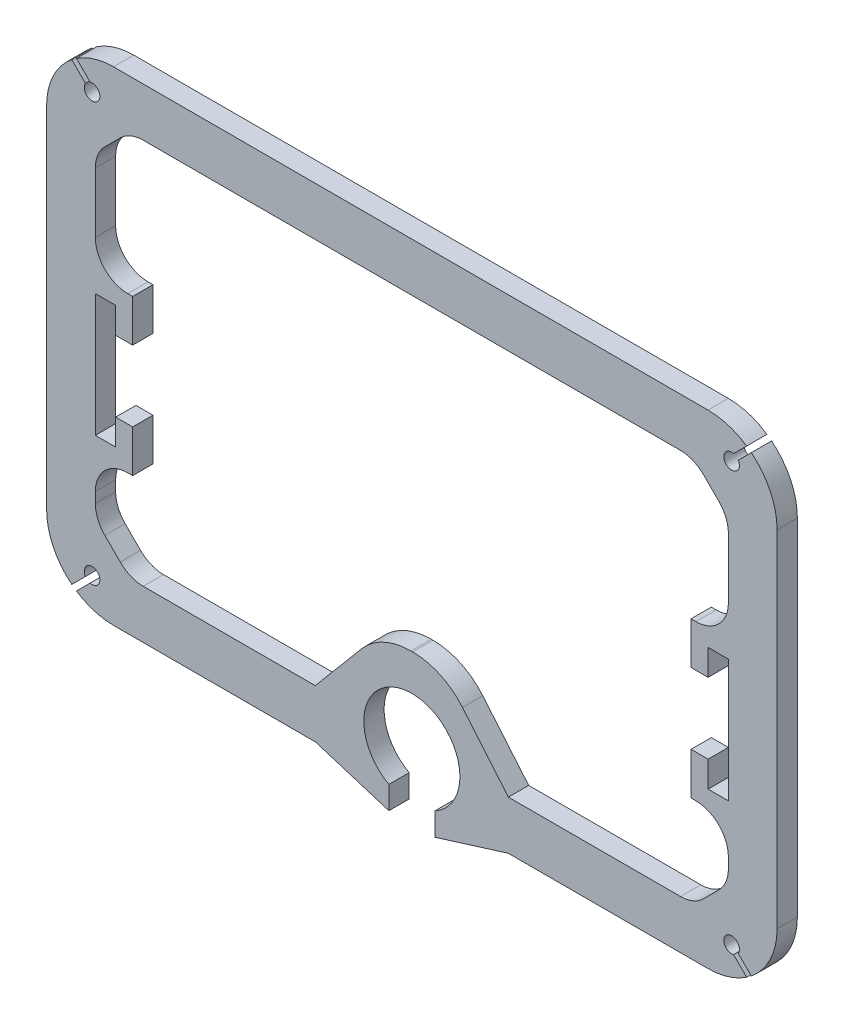
SolidWorks part; units mm, degrees
material "Delrin 2700 NC010, Low Viscosity Acetal Copolymer (SS)"
ref_plane "Front Plane" through (0, 0, 0) normal (0, 0, 1) x (1, 0, 0)
ref_plane "Top Plane" through (0, 0, 0) normal (0, 1, 0) x (1, 0, 0)
ref_plane "Right Plane" through (0, 0, 0) normal (1, 0, 0) x (0, 0, -1)
sketch "Sketch1" plane through (0, 0, 0) normal (0, 0, 1) x (1, 0, 0)
  line L0 (-23.3423, -18.923) -> (-7.5425, -18.923)
  line L1 (-24.765, 13.6903) -> (-24.765, -13.6903)
  line L2 (-23.3423, -15.113) -> (-7.5521, -15.113)
  line L3 (7.5521, -15.113) -> (23.1704, -15.113)
  line L4 (24.765, 13.5184) -> (24.765, -13.5184)
  line L5 (-1000, 0) -> (49000, 0) construction
  line L6 (-1.7968, -18.923) -> (-1.7968, -20.7107)
  line L7 (7.5425, -18.923) -> (23.1704, -18.923)
  line L8 (23.1704, 15.113) -> (-23.3423, 15.113)
  line L9 (-7.5521, -15.113) -> (-3.9596, -10.8316)
  line L10 (-28.575, 13.6903) -> (-28.575, -13.6903)
  line L11 (7.5521, -15.113) -> (3.9596, -10.8316)
  line L12 (-0.0681, -9.017) -> (0.0681, -9.017)
  line L13 (28.575, 13.5184) -> (28.575, -13.5184)
  line L14 (23.1704, 18.923) -> (-23.3423, 18.923)
  line L15 (1.7968, -18.923) -> (1.7968, -20.7107)
  line L16 (-7.5425, -18.923) -> (-1.7968, -20.7107)
  line L17 (7.5425, -18.923) -> (1.7968, -20.7107)
  line L18 (0, 12.5532) -> (0, -24.2768) construction
  line L19 (1.7968, -18.923) -> (23.1704, -18.923) construction
  line L20 (-23.3423, -18.923) -> (-1.7968, -18.923) construction
  line L21 (-24.765, 5.0849) -> (0, 5.0849) construction
  line L22 (0, 5.0849) -> (24.765, 5.0849) construction
  arc A0 (1.7968, -18.923) -> (-1.7968, -18.923) centre (0, -15.621) ccw
  arc A1 (-23.3423, -15.113) -> (-24.765, -13.6903) centre (-23.3423, -13.6903) cw
  arc A2 (-0.0681, -9.017) -> (-3.9596, -10.8316) centre (-0.0681, -14.097) ccw
  arc A3 (24.765, -13.5184) -> (23.1704, -15.113) centre (23.1704, -13.5184) cw
  arc A4 (23.1704, 15.113) -> (24.765, 13.5184) centre (23.1704, 13.5184) cw
  arc A5 (-23.3423, -18.923) -> (-28.575, -13.6903) centre (-23.3423, -13.6903) cw
  arc A6 (28.575, -13.5184) -> (23.1704, -18.923) centre (23.1704, -13.5184) cw
  arc A7 (23.1704, 18.923) -> (28.575, 13.5184) centre (23.1704, 13.5184) cw
  arc A8 (-23.3423, 18.923) -> (-28.575, 13.6903) centre (-23.3423, 13.6903) ccw
  circle A9 centre (-25.019, 16.383) radius 0.6096
  circle A10 centre (25.019, 16.383) radius 0.6096
  arc A11 (-23.3423, 15.113) -> (-24.765, 13.6903) centre (-23.3423, 13.6903) ccw
  arc A12 (0.0681, -9.017) -> (3.9596, -10.8316) centre (0.0681, -14.097) cw
  circle A13 centre (25.019, -16.383) radius 0.6096
  circle A14 centre (-25.019, -16.383) radius 0.6096
  circle A15 centre (0, -15.621) radius 5.3975 construction
  arc A18 (7.5521, -15.113) -> (-7.5521, -15.113) centre (0, -15.621) ccw construction
  point P0 (0, 0)
  dimension "D4" = 3.302
  dimension "D6" = 37.846
  dimension "D7" = 3.556
  dimension "D8" = 3.81
  dimension "D9" = 6.604
  dimension "D5" = 1.2192
  dimension "D2" = 49.53
  dimension "D3" = 7.5184
  dimension "D10" = 5.08
  dimension "D11" = 5.08
  dimension "D14" = 10.795
  dimension "D12" = 2.54
extrude "Boss-Extrude1" add sketch "Sketch1" along normal blind 1.5875
sketch "Sketch2" plane through (-24.765, 0, 0) normal (1, 0, 0) x (0, 0, -1)
  line L0 (0, 2.8448) -> (-1.5875, 2.8448)
  line L1 (0, -6.7596) -> (-1.5875, -6.7596) construction
  line L2 (-1.5875, -15.113) -> (0, -15.113)
  line L3 (-1.5875, -15.113) -> (0, -15.113) construction
  line L4 (0, -13.6903) -> (0, 13.6903)
  line L5 (0, 13.6903) -> (-1.5875, 13.6903)
  line L6 (-1.5875, 13.6903) -> (-1.5875, -13.6903)
  line L7 (0, 13.6903) -> (-1.5875, 13.6903)
  line L8 (0, -13.6903) -> (0, 4.1148)
  line L9 (-1.5875, -15.113) -> (-1.5875, -8.0296)
  line L10 (-1.5875, 4.1148) -> (-1.5875, -13.6903)
  line L11 (-1.5875, -13.6903) -> (0, -13.6903)
  line L12 (0, -15.113) -> (0, -8.0296)
  line L13 (0, 4.1148) -> (-1.5875, 4.1148)
  line L14 (-1.5875, 2.8448) -> (-1.5875, -6.6447)
  line L15 (-1.5875, 4.1148) -> (-1.5875, 2.8448)
  line L16 (0, 2.8448) -> (0, 4.1148)
  line L17 (0, -7.9147) -> (0, 1.4693)
  line L18 (-1.5875, -7.9147) -> (-1.5875, -6.6447)
  line L19 (0, -6.7596) -> (-1.5875, -6.7596)
  line L21 (0, -8.0296) -> (-1.5875, -8.0296)
  line L22 (0, -8.0296) -> (0, -13.6903)
  line L23 (-1.5875, -8.0296) -> (-1.5875, -13.6903)
  line L24 (47.9467, 2.8448) -> (1.4151, 2.8448) construction
  line L28 (-1.5875, -13.6903) -> (0, -13.6903)
  line L29 (47.5608, -9.6909) -> (1.4354, -6.848) construction
  line M5 (0, -13.6903) -> (0, 13.6903)
  line M7 (-1.5875, 13.6903) -> (-1.5875, -13.6903)
  dimension "D1" = 0
  dimension "D2" = 1.27
  dimension "D4" = 1.27
extrude "Boss-Extrude2" add sketch "Sketch2" along normal blind 2.921 contours L13 L10 L0 M5 | L19 L17 L8 L0 L10 M7 | L21 L8 L19 L18 M5 M7 region at (-24.765, -1.9574, 0.7937) region at (-24.765, 3.4798, 0.7937) region at (-24.765, -7.3946, 0.7937)
extrude "Cut-Extrude1" cut sketch "Sketch2<3>" along normal blind 1.5875 contours L19 L17 L0 M5 M7 region at (-24.765, -1.9574, 0.7937)
sketch "Sketch2<3>" plane through (-24.765, 0, 0) normal (1, 0, 0) x (0, 0, -1) same geometry as "Sketch2"
sketch "Sketch3" plane through (-23.1775, 0, 0) normal (-1, 0, 0) x (0, 0, 1)
  line L0 (0, 2.8448) -> (1.5875, 2.8448) construction
  line L1 (0, -6.7596) -> (1.5875, -6.7596) construction
  line L2 (0, 2.8448) -> (1.5875, 2.8448)
  line L3 (0, -6.7596) -> (1.5875, -6.7596)
  line L4 (0, 0.8128) -> (1.5875, 0.8128)
  line L5 (0, -4.7276) -> (1.5875, -4.7276)
  line L6 (1.5875, 0.8128) -> (1.5875, -4.7276)
  line L7 (0, -4.7276) -> (0, 0.8128)
  line M2 (1.5875, -6.7596) -> (1.5875, 2.8448)
  line M4 (0, 2.8448) -> (0, -6.7596)
  dimension "D1" = 2.032
  dimension "D2" = 2.032
extrude "Cut-Extrude2" cut sketch "Sketch3" against normal up to surface (1.3335 mm away) contours L5 L4 M4 M2 region at (-23.1775, -1.9574, 0.7937) up to face at (-21.844, -1.9574, 0.7937)
mirror "Mirror1" about plane through (0, 0, 0) normal (1, 0, 0) of "Cut-Extrude2", "Boss-Extrude2", "Cut-Extrude1"
fillet "Fillet5" radius 2.54 4 edges at (24.765, 4.1148, 0.7937) (24.765, -8.0296, 0.7937) (-24.765, -8.0296, 0.7937) (-24.765, 4.1148, 0.7937)
sketch "Sketch4" plane through (0, 0, 1.5875) normal (0, 0, 1) x (1, 0, 0)
  line L0 (-26.2434, 18.0452) -> (-25.1714, 16.9732)
  line L1 (-26.6067, 17.7799) -> (-25.5348, 16.708)
  line L2 (23.1704, 18.923) -> (-23.3423, 18.923) construction
  circle A0 centre (-25.019, 16.383) radius 0.6096 construction
  arc A1 (-23.3423, 18.923) -> (-28.575, 13.6903) centre (-23.3423, 13.6903) ccw construction
  arc A2 (-26.2434, 18.0452) -> (-26.6067, 17.7799) centre (-23.3423, 13.6903) ccw
  arc A3 (-25.1714, 16.9732) -> (-25.5348, 16.708) centre (-25.019, 16.383) ccw
  dimension "SnapInSlot" = 0.4445
  dimension "D2" = 45
extrude "Slot for installing carbon rod" cut sketch "Sketch4" against normal through all
sketch "Sketch5" plane through (0, 0, 1.5875) normal (0, 0, 1) x (1, 0, 0)
  line L0 (-24.765, 12.4203) -> (-22.0723, 15.113)
  line L1 (-24.765, 13.6903) -> (-24.765, 6.6548) construction
  line L2 (23.1704, 15.113) -> (-23.3423, 15.113) construction
  line L3 (-22.0723, 15.113) -> (-23.3423, 15.113)
  line L4 (-24.765, 13.6903) -> (-24.765, 12.4203)
  arc A0 (-23.3423, 15.113) -> (-24.765, 13.6903) centre (-23.3423, 13.6903) ccw construction
  arc A1 (-23.3423, 15.113) -> (-24.765, 13.6903) centre (-23.3423, 13.6903) ccw
  dimension "D1" = 1.27
extrude "Boss-Extrude3" add sketch "Sketch5" against normal up to surface (1.5875 mm away) up to face at (-0.0065, -2.9492, 0)
mirror "Mirror2" about plane through (0, 0, 0) normal (1, 0, 0) of "Boss-Extrude3", "Slot for installing carbon rod"
mirror "Mirror4" about plane through (0, 0, 0) normal (0, 1, 0) of "Mirror2", "Boss-Extrude3"
fillet "Fillet7" radius 2.54 8 edges at (22.0723, -15.113, 0.7937) (24.765, -12.4203, 0.7937) (-22.0723, -15.113, 0.7937) (-24.765, -12.4203, 0.7937) (24.765, 12.4203, 0.7937) (22.0723, 15.113, 0.7937) (-22.0723, 15.113, 0.7937) (-24.765, 12.4203, 0.7937)
